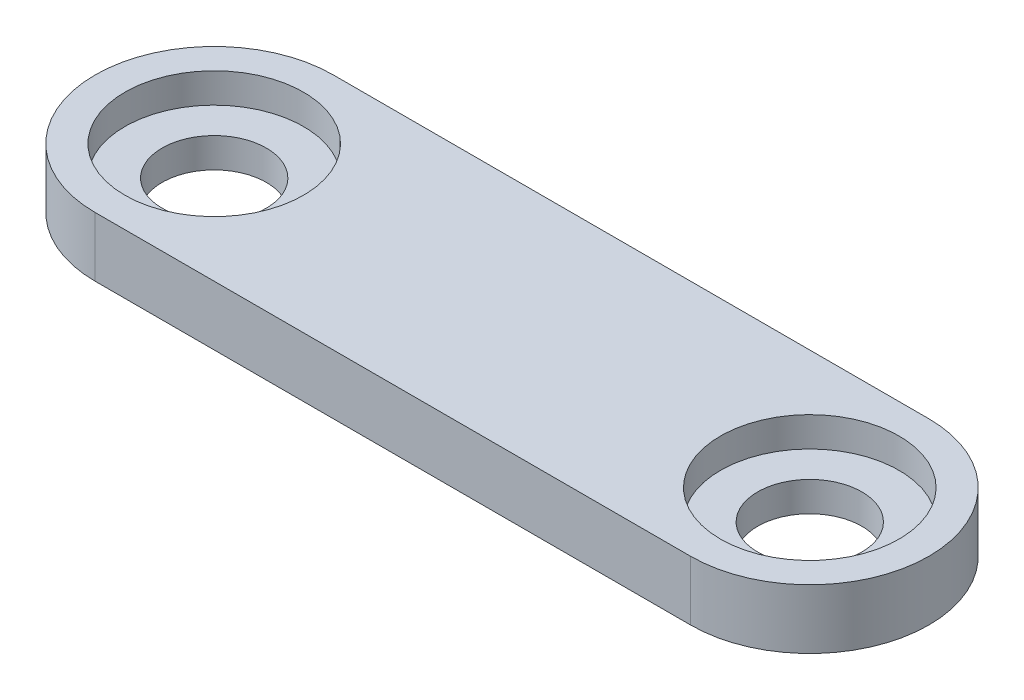
SolidWorks part; units mm, degrees
ref_plane "Front Plane" through (0, 0, 0) normal (0, 0, 1) x (1, 0, 0)
ref_plane "Top Plane" through (0, 0, 0) normal (0, 1, 0) x (1, 0, 0)
ref_plane "Right Plane" through (0, 0, 0) normal (1, 0, 0) x (0, 0, -1)
sketch "Sketch1" plane through (0, 0, 0) normal (0, 1, 0) x (1, 0, 0)
  line L0 (-10, 4) -> (10, 4)
  line L2 (10, -4) -> (-10, -4)
  arc A0 (10, -4) -> (10, 4) centre (10, 0) ccw
  arc A1 (-10, -4) -> (-10, 4) centre (-10, 0) cw
  circle A2 centre (-10, 0) radius 1.75
  circle A3 centre (10, 0) radius 1.75
  point P8 (0, -4)
  point P10 (0, 4)
  point P11 (0, 0)
  point P12 (0, 0)
  dimension "D2" = 3.5
  dimension "D3" = 3.5
  dimension "D1" = 8
  dimension "D4" = 20
extrude "Boss-Extrude1" add sketch "Sketch1" along normal blind 2
sketch "Sketch3" plane through (0, 2, 0) normal (0, 1, 0) x (1, 0, 0)
  circle A0 centre (-10, 0) radius 3
  circle A1 centre (10, 0) radius 3
  dimension "D1" = 6
  dimension "D2" = 6
extrude "Cut-Extrude1" cut sketch "Sketch3" against normal blind 1
